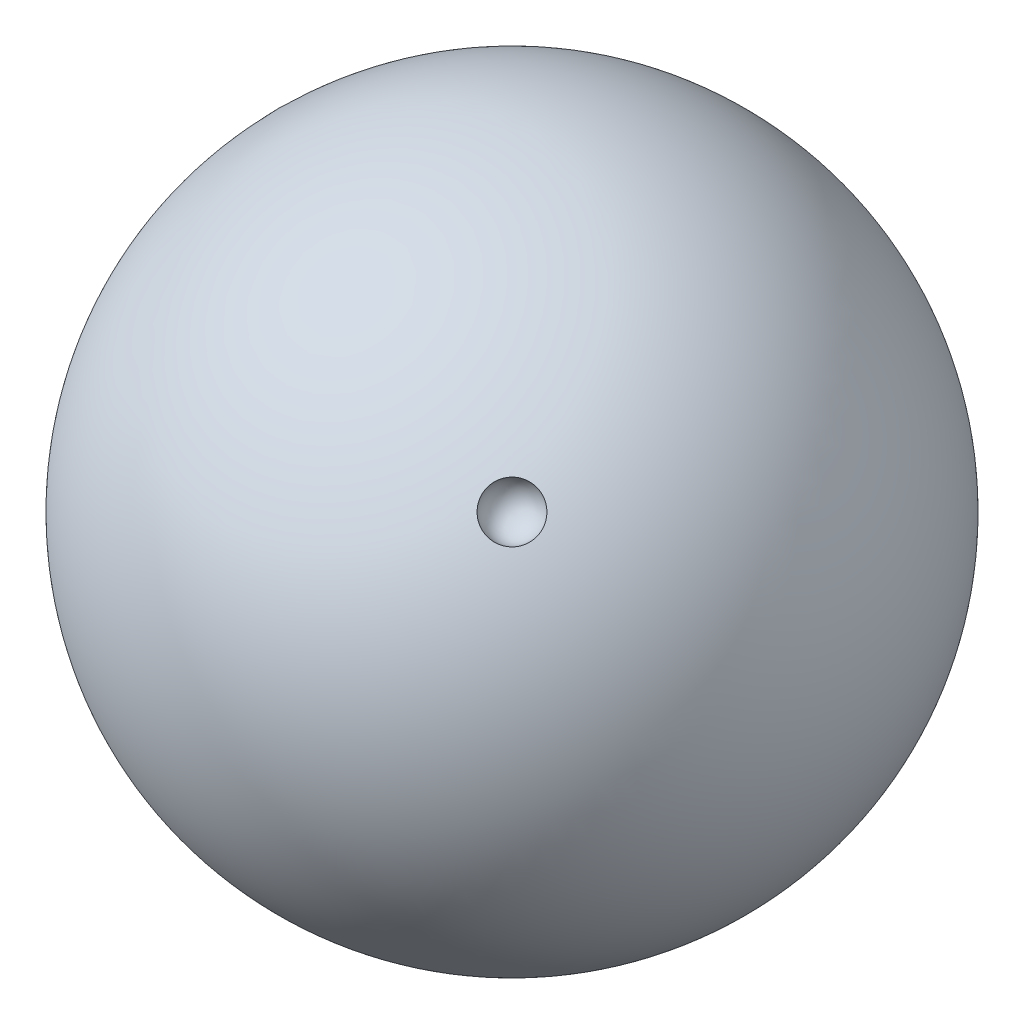
SolidWorks part; units mm, degrees
note: '?' marks a value the reader was unsure of.
ref_plane "Front Plane" through (0, 0, 0) normal (0, 0, 1) x (1, 0, 0)
ref_plane "Top Plane" through (0, 0, 0) normal (0, 1, 0) x (1, 0, 0)
ref_plane "Right Plane" through (0, 0, 0) normal (1, 0, 0) x (0, 0, -1)
other "Configuration Table"
sketch "Sketch1" plane through (0, 0, 0) normal (0, 0, 1) x (1, 0, 0)
  line L0 (0, 0) -> (0, 23448.3346) construction
  line L1 (0, 0) -> (23448.3346, 0) construction
  line L2 (0, 40) -> (0, -40)
  arc A1 (0, -40) -> (0, 40) centre (0, 0) ccw
  dimension "D1" = 80
revolve "Revolve1" add sketch "Sketch1" angle 360 about L0
ref_axis "Axis2" through (0, -44, 0) along (0, 1, 0)?
ref_plane "Plane2" through (0, 0, 0) normal (0.7071, 0, -0.7071) x (0, 1, 0)
ref_axis "Axis3" through (0, 0, -44) along (0, 0, 1)?
ref_plane "Plane3" through (0, 0, 0) normal (-0.7071, 0.7071, 0) x (0, 0, 1)
sketch3d "3DSketch1"
  point P0 (23.094, 23.094, 23.094)
ref_axis "Axis1" through (23.094, 23.094, 23.094) along (0.5774, 0.5774, 0.5774)?
ref_plane "Plane1" through (23.094, 23.094, 23.094) normal (0.5774, 0.5774, 0.5774) x (-0.4958, -0.3139, 0.8097)
sketch "Sketch3" plane through (23.094, 23.094, 23.094) normal (0.5774, 0.5774, 0.5774) x (-0.4958, -0.3139, 0.8097)
  line L0 (0, 0) -> (0, -22285.163) construction
  line L1 (0, 0) -> (22285.163, 0) construction
  line L2 (0, 3) -> (0, -3)
  arc A0 (0, -3) -> (0, 3) centre (0, 0) ccw
  dimension "D1" = 3
revolve "Cut-Revolve2" cut sketch "Sketch3" angle 360 about L0
